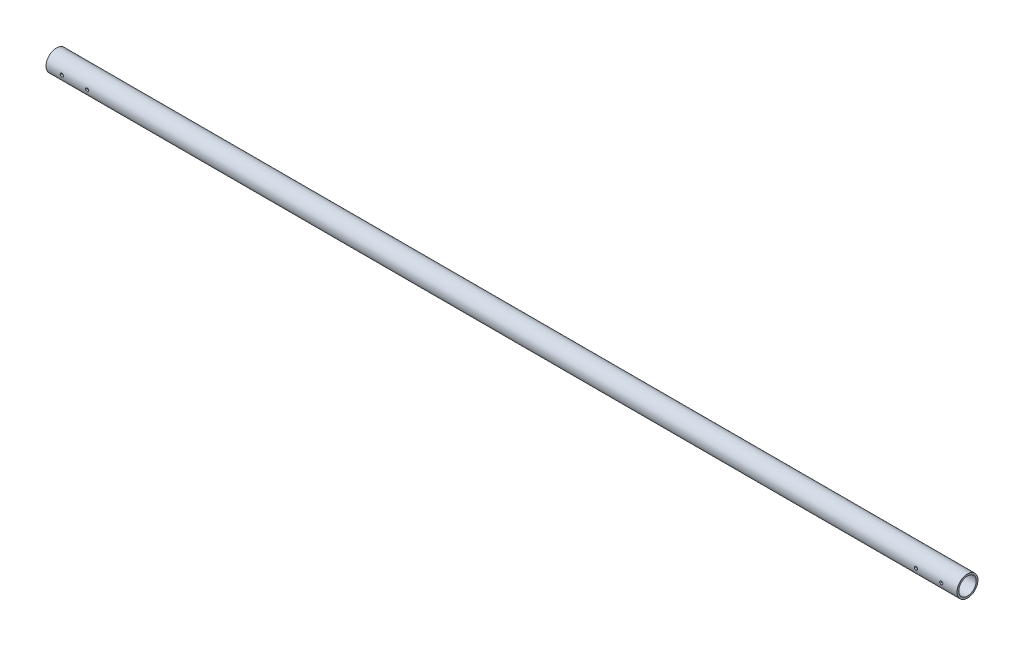
SolidWorks part; units mm, degrees
material "6061-T6 (SS)"
ref_plane "Front Plane" through (0, 0, 0) normal (0, 0, 1) x (1, 0, 0)
ref_plane "Top Plane" through (0, 0, 0) normal (0, 1, 0) x (1, 0, 0)
ref_plane "Right Plane" through (0, 0, 0) normal (1, 0, 0) x (0, 0, -1)
sketch "Sketch1" plane through (0, 0, 0) normal (1, 0, 0) x (0, 0, -1)
  circle A0 centre (0, 0) radius 21.082
  circle A1 centre (0, 0) radius 17.526
  dimension "D1" = 42.164
  dimension "D2" = 35.052
extrude "Boss-Extrude1" add sketch "Sketch1" along normal blind 914.4 and the other way blind 914.4
sketch "Sketch2" plane through (0, 0, 0) normal (0, 0, 1) x (1, 0, 0)
  line L0 (-914.4, 21.082) -> (-914.4, -21.082) construction
  circle A0 centre (-831.85, 0) radius 3.175
  circle A1 centre (-882.65, 0) radius 3.175
  dimension "D1" = 6.35
  dimension "D2" = 31.75
  dimension "D3" = 50.8
extrude "Cut-Extrude1" cut sketch "Sketch2" against normal through all both and the other way through all
mirror "Mirror1" about plane through (0, 0, 0) normal (1, 0, 0) of "Cut-Extrude1"
